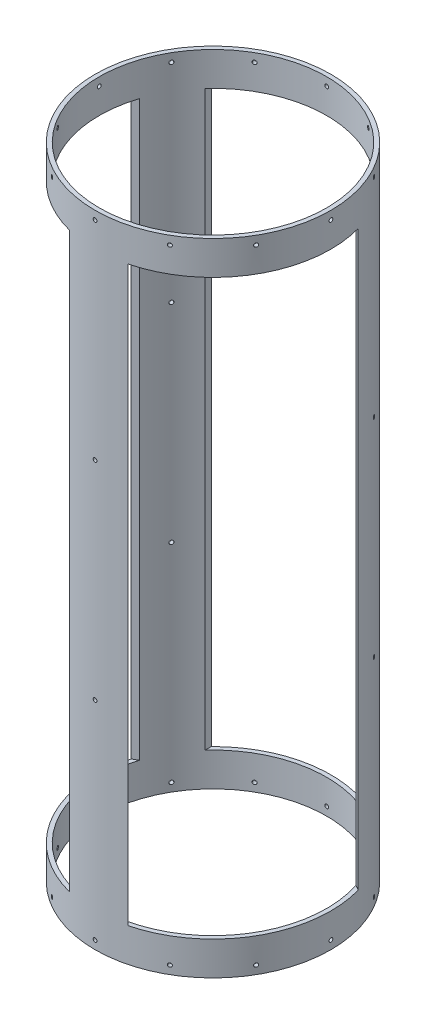
SolidWorks part; units mm, degrees
material "6061-T6 (SS)"
ref_plane "Front Plane" through (0, 0, 0) normal (0, 0, 1) x (1, 0, 0)
ref_plane "Top Plane" through (0, 0, 0) normal (0, 1, 0) x (1, 0, 0)
ref_plane "Right Plane" through (0, 0, 0) normal (1, 0, 0) x (0, 0, -1)
sketch "Sketch1" plane through (0, 0, 0) normal (0, 1, 0) x (1, 0, 0)
  circle A0 centre (0, 0) radius 88.9
  circle A1 centre (0, 0) radius 85.725
  dimension "D1" = 177.8
  dimension "D2" = 171.45
extrude "Boss-Extrude1" add sketch "Sketch1" along normal mid plane 482.854
sketch "Sketch2" plane through (0, 0, 0) normal (0, 0, 1) x (1, 0, 0)
  line L0 (85.725, 241.427) -> (-85.725, 241.427) construction
  line L1 (-63.5, -216.027) -> (63.5, -216.027)
  line L2 (-63.5, -216.027) -> (-63.5, 216.027)
  line L3 (-63.5, 216.027) -> (63.5, 216.027)
  line L4 (63.5, -216.027) -> (63.5, 216.027)
  line L5 (-63.5, -216.027) -> (63.5, 216.027) construction
  line L6 (-63.5, 216.027) -> (63.5, -216.027) construction
  line L7 (88.9, -241.427) -> (88.9, 241.427) construction
  point P0 (0, 0)
  dimension "D1" = 25.4
  dimension "D2" = 25.4
extrude "Cut-Extrude1" cut sketch "Sketch2" against normal up to surface (62.217 mm away) up to face at (0, 241.427, 88.9)
pattern_circular "CirPattern1" count 3 over 360 about axis through (0, 241.427, 0) along (0, -1, 0) of "Cut-Extrude1"
ref_plane "Plane1" through (88.9, 0, 0) normal (1, 0, 0) x (0, 0, -1)
sketch "Sketch4" plane through (88.9, 0, 0) normal (1, 0, 0) x (0, 0, -1)
  line L0 (0, 97.79) -> (0, -97.79) construction
  line L1 (88.9, 241.427) -> (-88.9, 241.427) construction
  circle A0 centre (0, 235.077) radius 1.4351
  dimension "D1" = 2.8702
  dimension "D2" = 6.35
extrude "Cut-Extrude3" cut sketch "Sketch4" against normal blind 15.24
pattern_circular "CirPattern3" count 12 over 360 about axis through (0, 241.427, 0) along (0, -1, 0) of "Cut-Extrude3"
mirror "Mirror1" about plane through (0, 0, 0) normal (0, 1, 0) of "Cut-Extrude3", "CirPattern3"
ref_plane "Plane2" through (0, 0, 88.9) normal (0, 0, 1) x (1, 0, 0)
sketch "Sketch5" plane through (0, 0, 88.9) normal (0, 0, 1) x (1, 0, 0)
  circle A0 centre (0, 78.359) radius 1.4351
  circle A1 centre (0, -78.359) radius 1.4351
  circle A2 centre (0, -235.077) radius 1.4351 construction
  circle A3 centre (0, 235.077) radius 1.4351 construction
  dimension "D1" = 156.718
  dimension "D2" = 156.718
  dimension "D3" = 2.8702
  dimension "D4" = 2.8702
extrude "Cut-Extrude4" cut sketch "Sketch5" against normal blind 22.86
pattern_circular "CirPattern4" count 3 over 360 about axis through (0, 241.427, 0) along (0, -1, 0) of "Cut-Extrude4"
